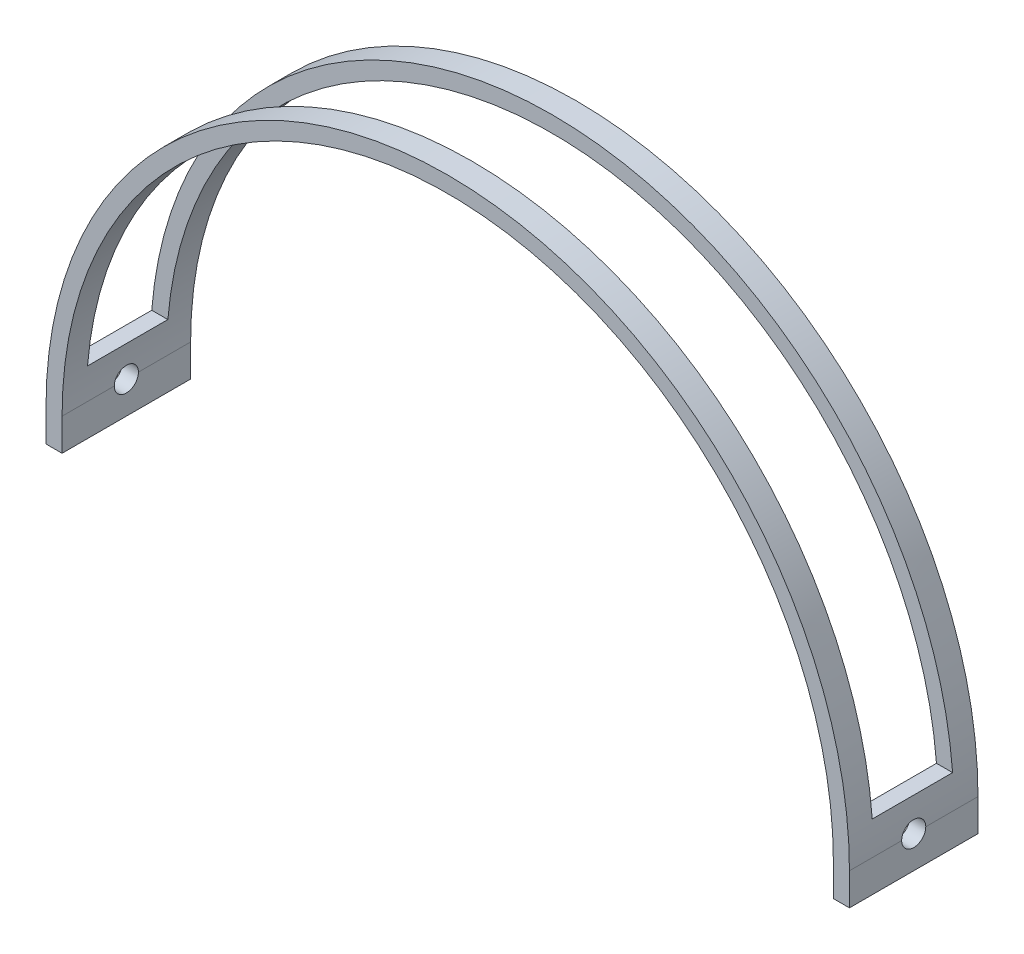
SolidWorks part; units mm, degrees
ref_plane "Front Plane" through (0, 0, 0) normal (0, 0, 1) x (1, 0, 0)
ref_plane "Top Plane" through (0, 0, 0) normal (0, 1, 0) x (1, 0, 0)
ref_plane "Right Plane" through (0, 0, 0) normal (1, 0, 0) x (0, 0, -1)
sketch "Sketch1" plane through (0, 0, 0) normal (0, 0, 1) x (1, 0, 0)
  line L0 (-250, 0) -> (250, 0) construction
  line L3 (-250, 0) -> (-250, -20)
  line L4 (-250, -20) -> (-240, -20)
  line L5 (-240, 0) -> (-240, -20)
  line L7 (240, 0) -> (240, -20)
  line L8 (240, -20) -> (250, -20)
  line L9 (250, 0) -> (250, -20)
  arc A0 (250, 0) -> (-250, 0) centre (0, 0) ccw
  arc A1 (240, 0) -> (-240, 0) centre (0, 0) ccw
  dimension "D1" = 240
  dimension "D2" = 250
  dimension "D3" = 20
extrude "Boss-Extrude1" add sketch "Sketch1" along normal blind 80
sketch "Sketch2" plane through (250, 0, 0) normal (1, 0, 0) x (0, 0, -1)
  line L0 (-80, 0) -> (0, 0) construction
  circle A0 centre (-40, 0) radius 7.5
  dimension "D1" = 15
extrude "Cut-Extrude2" cut sketch "Sketch2" against normal through all
sketch "Sketch4" plane through (250, 0, 0) normal (1, 0, 0) x (0, 0, -1)
  line L0 (-40, 250) -> (-40, 7.5) construction
  line L1 (0, 250) -> (-80, 250) construction
  line L4 (-65, 20) -> (-65, 250)
  line L5 (-65, 250) -> (-15, 250)
  line L6 (-15, 250) -> (-15, 20)
  line L8 (-32.5, 0) -> (0, 0) construction
  line L13 (-65, 20) -> (-15, 20)
  arc A1 (-32.5, 0) -> (-47.5, 0) centre (-40, 0) ccw construction
  dimension "D1" = 50
  dimension "D2" = 20
extrude "Cut-Extrude3" cut sketch "Sketch4" against normal through all
ref_point "Point1"
ref_point "Point2"
ref_axis "Axis1" through (-244.9713, 0.0005, 40) along (1, 0, 0)
